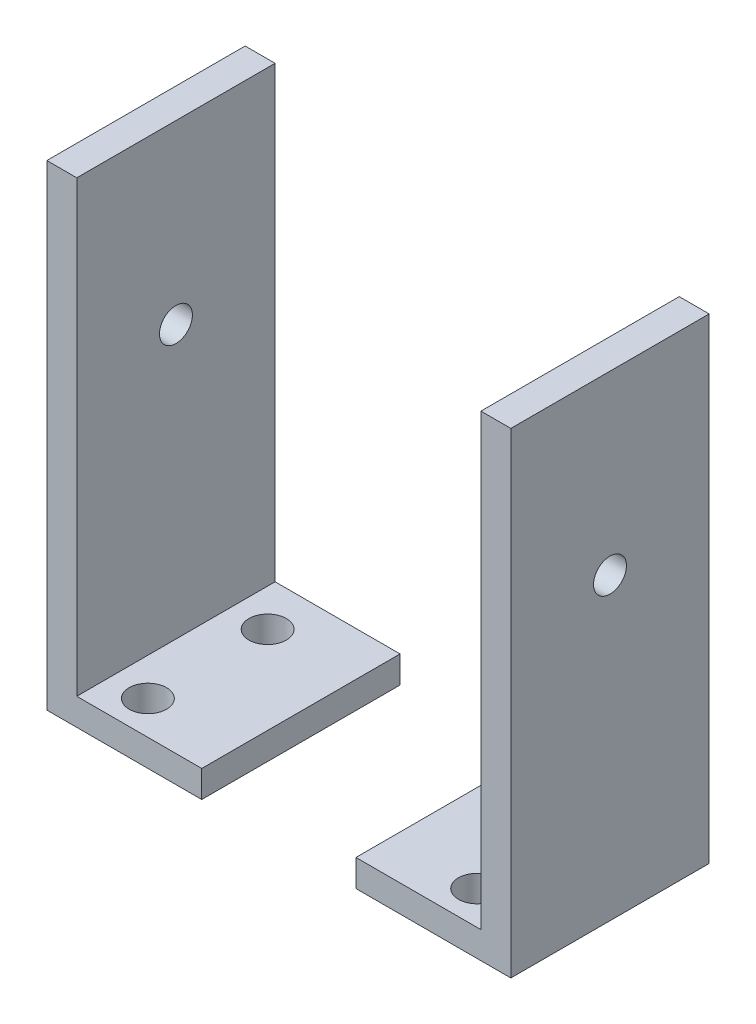
SolidWorks part; units mm, degrees
ref_plane "Front Plane" through (0, 0, 0) normal (0, 0, 1) x (1, 0, 0)
ref_plane "Top Plane" through (0, 0, 0) normal (0, 1, 0) x (1, 0, 0)
ref_plane "Right Plane" through (0, 0, 0) normal (1, 0, 0) x (0, 0, -1)
sketch "Sketch1" plane through (0, 0, 0) normal (0, 1, 0) x (1, 0, 0)
  line L0 (0, 6.25) -> (31, 6.25) construction
  line L5 (0, 0) -> (31, 0)
  line L6 (0, 0) -> (0, 13.25)
  line L7 (0, 13.25) -> (31, 13.25)
  line L8 (31, 0) -> (31, 13.25)
  circle A0 centre (4.5, 2.25) radius 1.25
  circle A1 centre (26.5, 2.25) radius 1.25
  circle A2 centre (26.5, 10.25) radius 1.25
  circle A3 centre (4.5, 10.25) radius 1.25
  dimension "D3" = 2.5
  dimension "D4" = 2.5
  dimension "D5" = 22
  dimension "D1" = 4.5
  dimension "D2" = 4.5
  dimension "D6" = 2.25
  dimension "D7" = 4
  dimension "D8" = 3
extrude "Boss-Extrude1" add sketch "Sketch1" along normal blind 1.8
sketch "Sketch2" plane through (0, 1.8, 0) normal (0, 1, 0) x (1, 0, 0)
  line L1 (0, 13.25) -> (2, 13.25)
  line L2 (0, 13.25) -> (0, 0)
  line L3 (0, 0) -> (2, 0)
  line L4 (2, 13.25) -> (2, 0)
  line L5 (15.5, 13.25) -> (15.5, 0) construction
  line L6 (29, 13.25) -> (31, 13.25)
  line L7 (29, 13.25) -> (29, 0)
  line L8 (29, 0) -> (31, 0)
  line L9 (31, 13.25) -> (31, 0)
  line L10 (31, 13.25) -> (0, 13.25) construction
  line L11 (0, 0) -> (31, 0) construction
  dimension "D1" = 13.5
  dimension "D2" = 2
  dimension "D4" = 27
  dimension "D5" = 2
  dimension "D7" = 13.5
sketch "Sketch4" plane through (0, 0, 0) normal (0, -1, 0) x (1, 0, 0)
  circle A0 centre (4.5, -2.25) radius 1.25
  circle A1 centre (26.5, -2.25) radius 1.25
  circle A2 centre (26.5, -10.25) radius 1.25
  circle A3 centre (4.5, -10.25) radius 1.25
extrude "Boss-Extrude2" add sketch "Sketch4" along normal blind 5 separate body
extrude "Boss-Extrude4" add sketch "Sketch4<4>" against normal blind 1.8
sketch "Sketch4<4>" plane through (0, 0, 0) normal (0, -1, 0) x (1, 0, 0) same geometry as "Sketch4"
extrude "Boss-Extrude5" add sketch "Sketch2" along normal blind 30
sketch "Sketch6" plane through (0, 1.8, 0) normal (0, 1, 0) x (1, 0, 0)
  line L0 (29, 13.25) -> (2, 13.25) construction
  line L1 (2, 0) -> (2, 13.25) construction
  line L2 (2, 0) -> (29, 0) construction
  line L3 (10.3492, 13.25) -> (20.6508, 13.25)
  line L4 (10.3492, 13.25) -> (10.3492, 0)
  line L5 (10.3492, 0) -> (20.6508, 0)
  line L6 (20.6508, 13.25) -> (20.6508, 0)
  point P2 (15.5, 13.25)
  point P11 (15.5, 13.25)
  dimension "D1" = 13.5
extrude "Cut-Extrude1" cut sketch "Sketch6" against normal up to surface (1.8 mm away) up to face at (4.5, 0, -11.5)
sketch "Sketch7" plane through (31, 0, 0) normal (1, 0, 0) x (0, 0, -1)
  line L0 (0, 0) -> (13.25, 0) construction
  line L3 (0, 31.8) -> (13.25, 31.8) construction
  circle A0 centre (6.625, 20) radius 1.1
  point P10 (6.625, 31.8)
  dimension "D1" = 2.2
  dimension "D2" = 20
extrude "Cut-Extrude2" cut sketch "Sketch7" against normal up to surface (31 mm away) up to face at (0, 15.9, -6.625)
extrude "Cut-Extrude3" cut sketch "Sketch4<5>" against normal blind 10
sketch "Sketch4<5>" plane through (0, 0, 0) normal (0, -1, 0) x (1, 0, 0) same geometry as "Sketch4"
delete or keep bodies "Body-Delete/Keep 1" type delete bodies bodies 119 120 121 118
